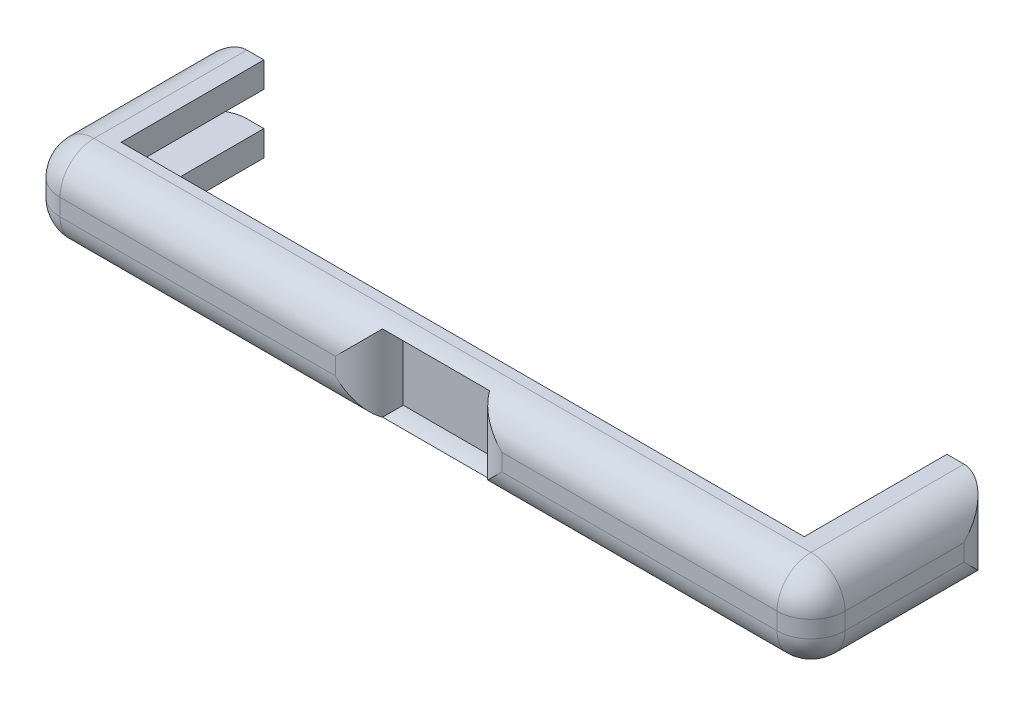
SolidWorks part; units mm, degrees
note: The reader was unsure of these and kept them because the rebuilt part matched: shared geometry of "Sketch1<3>", "Sketch1<4>".
ref_plane "Front Plane" through (0, 0, 0) normal (0, 0, 1) x (1, 0, 0)
ref_plane "Top Plane" through (0, 0, 0) normal (0, 1, 0) x (1, 0, 0)
ref_plane "Right Plane" through (0, 0, 0) normal (1, 0, 0) x (0, 0, -1)
sketch "Sketch1" plane through (0, 0, 0) normal (0, 0, 1) x (1, 0, 0)
  line L0 (-73.7719, 3.6591) -> (147.2281, -21.3409) construction
  line L1 (-73.7719, 3.6591) -> (147.2281, 3.6591)
  line L2 (-73.7719, 3.6591) -> (-73.7719, -21.3409) construction
  line L3 (-73.7719, -21.3409) -> (147.2281, -21.3409)
  line L4 (147.2281, 3.6591) -> (147.2281, -21.3409) construction
  line L5 (147.2281, 3.6591) -> (-73.7719, -21.3409) construction
  line L6 (-73.7719, -21.3409) -> (-78.7719, -21.3409)
  line L7 (22.2281, -18.8409) -> (51.2281, -18.8409)
  line L8 (22.2281, -18.8409) -> (22.2281, 1.1591)
  line L9 (22.2281, 1.1591) -> (51.2281, 1.1591)
  line L10 (51.2281, -18.8409) -> (51.2281, 1.1591)
  line L11 (22.2281, -18.8409) -> (51.2281, 1.1591) construction
  line L12 (22.2281, 1.1591) -> (51.2281, -18.8409) construction
  line L13 (-78.7719, -21.3409) -> (-78.7719, 3.6591)
  line L14 (-78.7719, 3.6591) -> (-73.7719, 3.6591)
  line L15 (-73.7719, -3.8409) -> (-63.7719, -3.8409)
  line L16 (-63.7719, -3.8409) -> (-63.7719, 3.6591)
  line L17 (-73.7719, -13.8409) -> (-63.7719, -13.8409)
  line L18 (-63.7719, -13.8409) -> (-63.7719, -21.3409)
  line L19 (-73.7719, -13.8409) -> (-73.7719, -3.8409)
  line L20 (137.2281, 3.6591) -> (137.2281, -3.8409)
  line L21 (137.2281, -3.8409) -> (147.2281, -3.8409)
  line L22 (147.2281, -3.8409) -> (147.2281, -13.8409)
  line L23 (147.2281, -13.8409) -> (137.2281, -13.8409)
  line L24 (137.2281, -13.8409) -> (137.2281, -21.3409)
  line L25 (147.2281, -21.3409) -> (152.2281, -21.3409)
  line L26 (152.2281, -21.3409) -> (152.2281, 3.6591)
  line L27 (152.2281, 3.6591) -> (147.2281, 3.6591)
  point P4 (36.7281, -8.8409)
  point P9 (-73.7719, -8.8409)
  point P10 (147.2281, -8.8409)
  point P11 (-73.7719, -3.8409)
  point P22 (0, 0)
  point P29 (0, 0)
  point P30 (0, 0)
  dimension "D1" = 221
  dimension "D2" = 25
  dimension "D3" = 29
  dimension "D4" = 20
  dimension "D5" = 5
  dimension "D7" = 10
  dimension "D8" = 10
extrude "Boss-Extrude1" add sketch "Sketch1" against normal blind 45
extrude "Boss-Extrude2" add sketch "Sketch1<3>" along normal blind 10
sketch "Sketch1<3>" plane through (0, 0, 0) normal (0, 0, 1) x (1, 0, 0) same geometry as "Sketch1"
extrude "Boss-Extrude3" add sketch "Sketch1<4>" against normal blind 3
sketch "Sketch1<4>" plane through (0, 0, 0) normal (0, 0, 1) x (1, 0, 0) same geometry as "Sketch1"
fillet "Fillet1" radius 10 8 edges at (36.7281, 1.1591, 10) (22.2281, -8.8409, 10) (36.7281, -18.8409, 10) (51.2281, -8.8409, 10) (-78.7719, -8.8409, 10) (36.7281, 3.6591, 10) (152.2281, -8.8409, 10) (36.7281, -21.3409, 10)
fillet "Fillet2" radius 10 5 edges at (149.2992, -18.412, 7.0711) (149.2992, 0.7302, 7.0711) (152.2281, -8.8409, -45) (152.2281, -21.3409, -22.5) (152.2281, 3.6591, -22.5)
fillet "Fillet3" radius 10 5 edges at (-78.7719, -21.3409, -22.5) (-78.7719, -8.8409, -45) (-78.7719, 3.6591, -22.5) (-75.8429, 0.7302, 7.0711) (-75.8429, -18.412, 7.0711)
